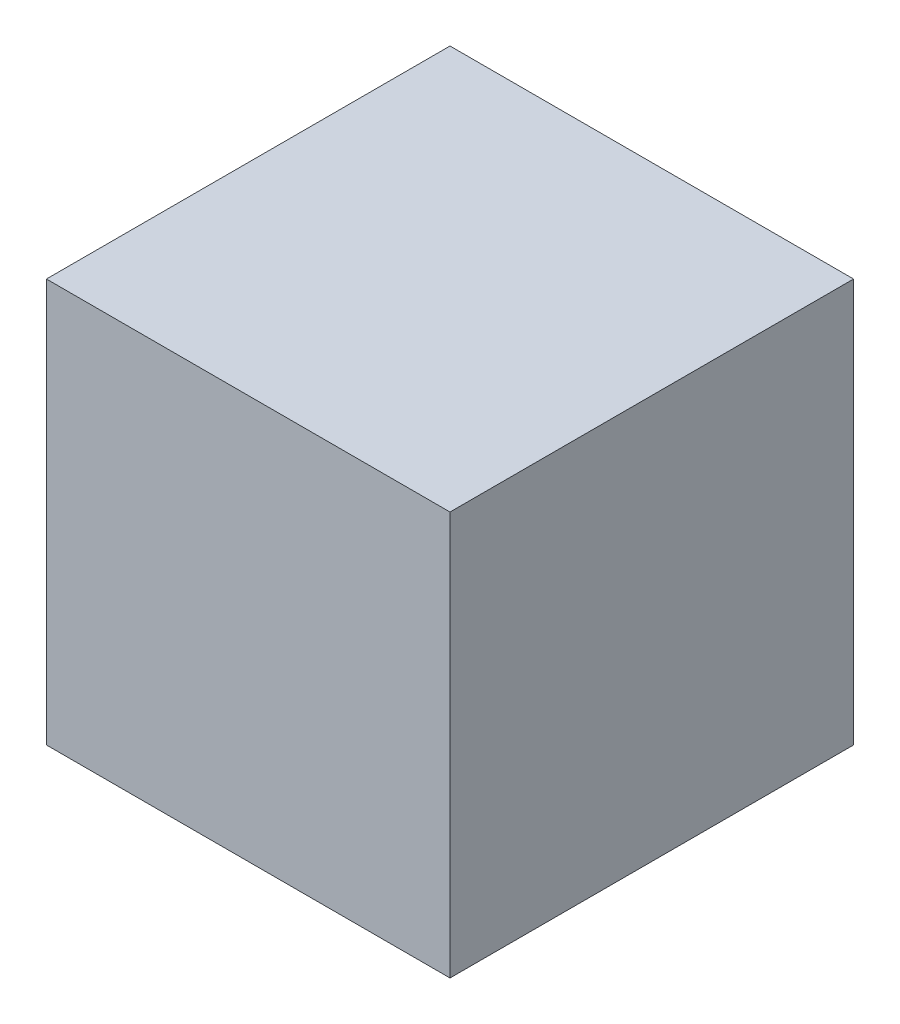
SolidWorks part; units mm, degrees
ref_plane "Front Plane" through (0, 0, 0) normal (0, 0, 1) x (1, 0, 0)
ref_plane "Top Plane" through (0, 0, 0) normal (0, 1, 0) x (1, 0, 0)
ref_plane "Right Plane" through (0, 0, 0) normal (1, 0, 0) x (0, 0, -1)
sketch "Sketch1" plane through (0, 0, 0) normal (0, 0, 1) x (1, 0, 0)
  line L0 (-60, 60) -> (60, -60) construction
  line L1 (-60, 60) -> (60, 60)
  line L2 (-60, 60) -> (-60, -60)
  line L3 (-60, -60) -> (60, -60)
  line L4 (60, 60) -> (60, -60)
  dimension "D1" = 120
extrude "Boss-Extrude1" add sketch "Sketch1" along normal blind 60 and the other way blind 60
